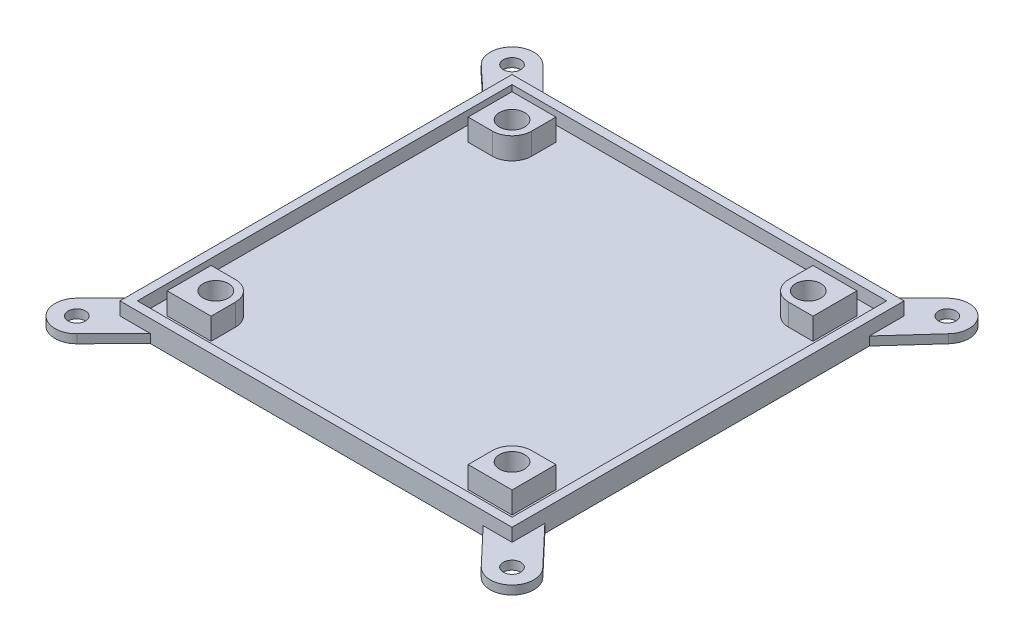
SolidWorks part; units mm, degrees
note: The reader was unsure of these and kept them because the rebuilt part matched: shared geometry of "Sketch1<3>", "Sketch1<9>", "Sketch1<10>".
ref_plane "Front Plane" through (0, 0, 0) normal (0, 0, 1) x (1, 0, 0)
ref_plane "Top Plane" through (0, 0, 0) normal (0, 1, 0) x (1, 0, 0)
ref_plane "Right Plane" through (0, 0, 0) normal (1, 0, 0) x (0, 0, -1)
sketch "Sketch1" plane through (0, 0, 0) normal (0, 1, 0) x (1, 0, 0)
  line L0 (-168.5609, -191.1478) -> (-170.5609, -191.1478)
  line L33 (-168.5609, -191.1478) -> (-258.5609, -191.1478)
  line L34 (-168.5609, -191.1478) -> (-168.5609, -101.1478)
  line L35 (-168.5609, -101.1478) -> (-258.5609, -101.1478)
  line L36 (-258.5609, -191.1478) -> (-258.5609, -101.1478)
  line L41 (-170.5609, -189.1478) -> (-256.5609, -189.1478)
  line L42 (-170.5609, -189.1478) -> (-170.5609, -103.1478)
  line L43 (-170.5609, -103.1478) -> (-256.5609, -103.1478)
  line L44 (-256.5609, -189.1478) -> (-256.5609, -103.1478)
  line L45 (-170.5609, -191.1478) -> (-170.5609, -189.1478)
  line L46 (-170.5609, -189.1478) -> (-173.9809, -189.1478)
  line L47 (-173.9809, -189.1478) -> (-173.9809, -185.7278)
  line L48 (-173.9809, -185.7278) -> (-176.0609, -185.7278)
  line L49 (-173.9809, -185.7278) -> (-253.1409, -185.7278)
  line L50 (-173.9809, -185.7278) -> (-173.9809, -106.5678)
  line L51 (-173.9809, -106.5678) -> (-253.1409, -106.5678)
  line L52 (-253.1409, -185.7278) -> (-253.1409, -106.5678)
  line L53 (-176.0609, -185.7278) -> (-176.0609, -183.6478)
  line L54 (-176.0609, -183.6478) -> (-179.5609, -183.6478)
  line L55 (-176.0609, -183.6478) -> (-251.0609, -183.6478)
  line L56 (-176.0609, -183.6478) -> (-176.0609, -108.6478)
  line L57 (-176.0609, -108.6478) -> (-251.0609, -108.6478)
  line L58 (-251.0609, -183.6478) -> (-251.0609, -108.6478)
  line L59 (-179.5609, -183.6478) -> (-179.5609, -180.1478)
  line L60 (-184.0609, -180.1478) -> (-184.0609, -183.6478)
  line L61 (-179.5609, -175.6478) -> (-176.0609, -175.6478)
  line L62 (-251.0609, -183.6478) -> (-247.5609, -183.6478)
  line L63 (-247.5609, -183.6478) -> (-247.5609, -180.1478)
  line L64 (-243.0609, -180.1478) -> (-243.0609, -183.6478)
  line L65 (-247.5609, -175.6478) -> (-251.0609, -175.6478)
  line L66 (-251.0609, -108.6478) -> (-251.0609, -112.1478)
  line L67 (-251.0609, -112.1478) -> (-247.5609, -112.1478)
  line L68 (-247.5609, -116.6478) -> (-251.0609, -116.6478)
  line L69 (-243.0609, -112.1478) -> (-243.0609, -108.6478)
  line L70 (-176.0609, -108.6478) -> (-179.5609, -108.6478)
  line L71 (-179.5609, -108.6478) -> (-179.5609, -112.1478)
  line L72 (-179.5609, -116.6478) -> (-176.0609, -116.6478)
  line L73 (-184.0609, -112.1478) -> (-184.0609, -108.6478)
  line L74 (-251.0609, -116.6478) -> (-253.1409, -116.6478)
  line L75 (-243.0609, -108.6478) -> (-243.0609, -106.5678)
  line L76 (-243.0609, -183.6478) -> (-243.0609, -185.7278)
  line L77 (-251.0609, -175.6478) -> (-253.1409, -175.6478)
  line L78 (-184.0609, -108.6478) -> (-184.0609, -106.5678)
  line L79 (-176.0609, -116.6478) -> (-173.9809, -116.6478)
  line L80 (-184.0609, -183.6478) -> (-184.0609, -185.7278)
  line L81 (-176.0609, -175.6478) -> (-173.9809, -175.6478)
  circle A0 centre (-179.5609, -180.1478) radius 2.9
  arc A4 (-184.0609, -180.1478) -> (-179.5609, -175.6478) centre (-179.5609, -180.1478) cw
  circle A5 centre (-247.5609, -180.1478) radius 2.9
  arc A6 (-247.5609, -175.6478) -> (-243.0609, -180.1478) centre (-247.5609, -180.1478) cw
  circle A9 centre (-247.5609, -112.1478) radius 2.9
  arc A10 (-247.5609, -116.6478) -> (-243.0609, -112.1478) centre (-247.5609, -112.1478) ccw
  circle A14 centre (-179.5609, -112.1478) radius 2.9
  arc A15 (-179.5609, -116.6478) -> (-184.0609, -112.1478) centre (-179.5609, -112.1478) cw
  dimension "D1" = 90
  dimension "D5" = 86
  dimension "D7" = 75
  dimension "D8" = 75
  dimension "D3" = 79.16
  dimension "D4" = 79.16
  dimension "D2" = 90
  dimension "D6" = 86
extrude "Boss-Extrude1" add sketch "Sketch1" along normal blind 5
extrude "Boss-Extrude2" add sketch "Sketch1<3>" along normal blind 2
sketch "Sketch1<3>" plane through (0, 0, 0) normal (0, 1, 0) x (1, 0, 0) same geometry as "Sketch1"
sketch "Sketch2" plane through (0, 0, 0) normal (0, -1, 0) x (1, 0, 0)
  line L0 (-168.5609, 101.1478) -> (-163.6111, 96.198)
  line L1 (-159.9062, 99.5556) -> (-168.5609, 109.1058)
  line L2 (-168.5609, 191.1478) -> (-168.5609, 101.1478) construction
  line L3 (-167.3161, 92.8405) -> (-175.6234, 101.1478)
  line L4 (-168.5609, 101.1478) -> (-258.5609, 101.1478) construction
  line L5 (-175.6234, 101.1478) -> (-168.5609, 101.1478)
  line L6 (-168.5609, 109.1058) -> (-168.5609, 101.1478)
  line L7 (-258.5609, 101.1478) -> (-263.5106, 96.198)
  line L8 (-266.9207, 99.8548) -> (-258.5609, 107.6506)
  line L9 (-258.5609, 191.1478) -> (-258.5609, 101.1478) construction
  line L10 (-260.1006, 92.5413) -> (-251.4941, 101.1478)
  line L11 (-251.4941, 101.1478) -> (-258.5609, 101.1478)
  line L12 (-258.5609, 107.6506) -> (-258.5609, 101.1478)
  line L13 (-258.5609, 191.1478) -> (-263.5106, 196.0975)
  line L14 (-259.9532, 199.611) -> (-251.5946, 191.1478)
  line L15 (-168.5609, 191.1478) -> (-258.5609, 191.1478) construction
  line L16 (-267.0681, 192.584) -> (-258.5609, 183.9704)
  line L17 (-258.5609, 183.9704) -> (-258.5609, 191.1478)
  line L18 (-251.5946, 191.1478) -> (-258.5609, 191.1478)
  line L19 (-168.5609, 191.1478) -> (-163.6111, 196.0975)
  line L20 (-167.2392, 199.5381) -> (-175.1958, 191.1478)
  line L21 (-175.1958, 191.1478) -> (-168.5609, 191.1478)
  line L22 (-159.9831, 192.657) -> (-168.5609, 183.6117)
  line L23 (-168.5609, 183.6117) -> (-168.5609, 191.1478)
  circle A0 centre (-163.6111, 96.198) radius 2
  arc A1 (-159.9062, 99.5556) -> (-167.3161, 92.8405) centre (-163.6111, 96.198) cw
  circle A2 centre (-263.5106, 96.198) radius 2
  arc A3 (-266.9207, 99.8548) -> (-260.1006, 92.5413) centre (-263.5106, 96.198) ccw
  circle A4 centre (-263.5106, 196.0975) radius 2
  arc A5 (-267.0681, 192.584) -> (-259.9532, 199.611) centre (-263.5106, 196.0975) cw
  circle A6 centre (-163.6111, 196.0975) radius 2
  arc A7 (-167.2392, 199.5381) -> (-159.9831, 192.657) centre (-163.6111, 196.0975) cw
extrude "Boss-Extrude11" add sketch "Sketch1<9>" along normal blind 7
sketch "Sketch1<9>" plane through (0, 0, 0) normal (0, 1, 0) x (1, 0, 0) same geometry as "Sketch1"
extrude "Boss-Extrude12" add sketch "Sketch1<10>" along normal blind 2 contours L57 L78 L51 L75 | L56 L81 L50 L79 | L80 L55 L76 L49 | L77 L58 L74 L52 | L72 A15 L73 L57 L69 A10 L68 L58 L65 A6 L64 L55 L60 A4 L61 L56
sketch "Sketch1<10>" plane through (0, 0, 0) normal (0, 1, 0) x (1, 0, 0) same geometry as "Sketch1"
extrude "Boss-Extrude13" add sketch "Sketch2" against normal blind 2
